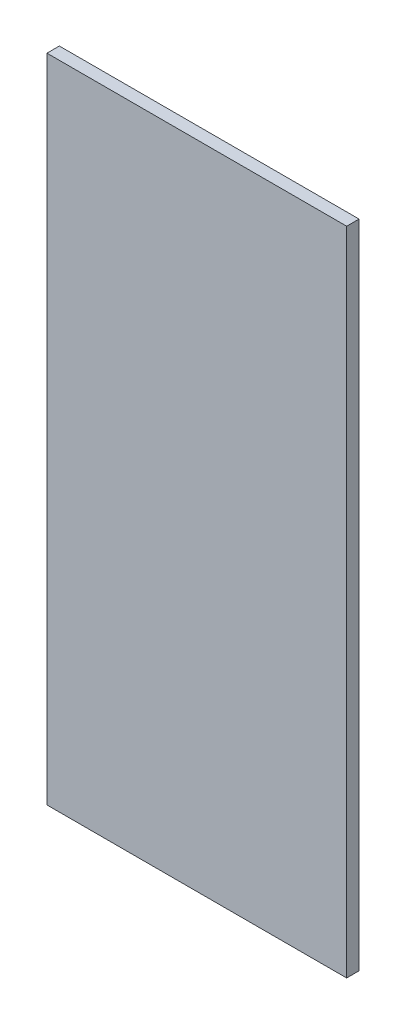
SolidWorks part; units mm, degrees
material "Perspex (TM) GS Acrylic Cast Sheet"
ref_plane "Front Plane" through (0, 0, 0) normal (0, 0, 1) x (1, 0, 0)
ref_plane "Top Plane" through (0, 0, 0) normal (0, 1, 0) x (1, 0, 0)
ref_plane "Right Plane" through (0, 0, 0) normal (1, 0, 0) x (0, 0, -1)
sketch "Sketch1" plane through (0, 0, 0) normal (0, 0, 1) x (1, 0, 0)
  line L1 (-72.5, -157.5) -> (72.5, -157.5)
  line L2 (-72.5, -157.5) -> (-72.5, 157.5)
  line L3 (-72.5, 157.5) -> (72.5, 157.5)
  line L4 (72.5, -157.5) -> (72.5, 157.5)
  line L5 (-72.5, -157.5) -> (72.5, 157.5) construction
  line L6 (-72.5, 157.5) -> (72.5, -157.5) construction
  point P0 (0, 0)
  dimension "D1" = 145
  dimension "D2" = 315
extrude "Boss-Extrude1" add sketch "Sketch1" along normal blind 6
equation "\"PCLength\"= 145mm'Length across I/O from PS to GPU"
equation "\"PCWidth\"= 340mm'Distance of longest part parallel to GPU(ussually GPU)"
equation "\"PCHeight\"= 180mm'Tallest point with mobo laying flat"
equation "\"WallThickness\"= 9mm'Thickness of each outer tank wall"
equation "\"ThermoBarrierThickness\"= 6mm'Thickness of barrier between hot side and cold side"
equation "\"HotSideGap\"= 36mm'Space in the hot side for a pump"
equation "\"PCClearance\"= 30mm'Clearance from top of tank to top of PC"
equation "\"RadiatorHeight\"= 275mm'Final Height from ground of radiators"
equation "\"D1@Sketch1\"=\"PCLength\""
equation "\"D2@Sketch1\"=\"RadiatorHeight\" + 40"
equation "\"D1@Boss-Extrude1\"=\"ThermoBarrierThickness\""
